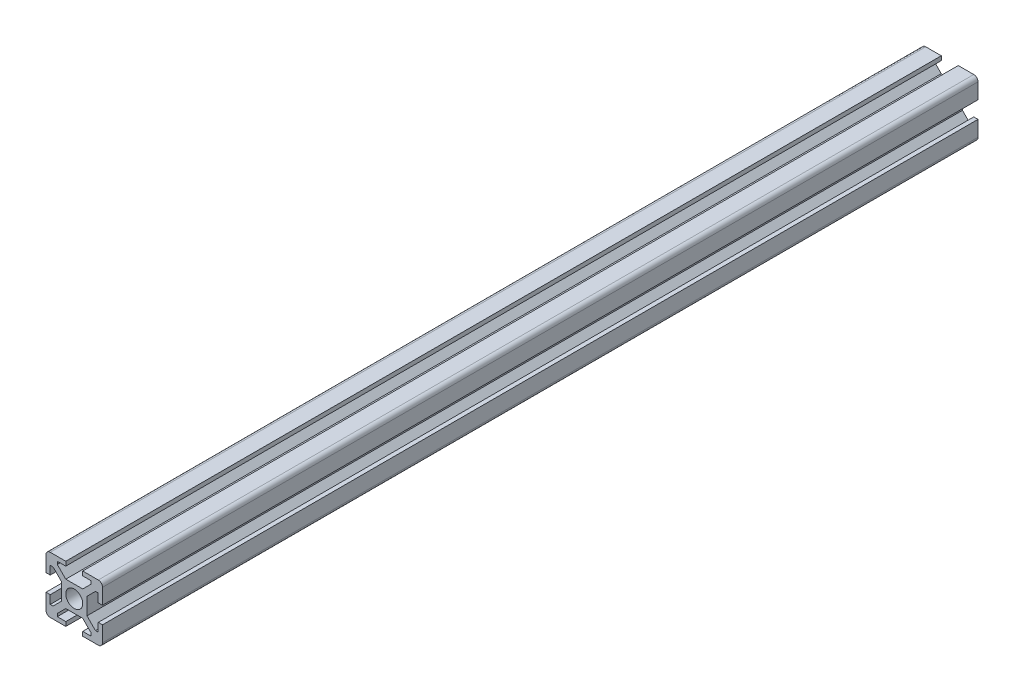
SolidWorks part; units mm, degrees
ref_plane "Plan de face" through (0, 0, 0) normal (0, 0, 1) x (1, 0, 0)
ref_plane "Plan de dessus" through (0, 0, 0) normal (0, 1, 0) x (1, 0, 0)
ref_plane "Plan de droite" through (0, 0, 0) normal (1, 0, 0) x (0, 0, -1)
sketch "Esquisse1" plane through (0, 0, 0) normal (0, 0, 1) x (1, 0, 0)
  line L0 (-10, 10) -> (10, -10) construction
  line L1 (-10, 10) -> (10, 10)
  line L2 (-10, 10) -> (-10, -10)
  line L3 (-10, -10) -> (10, -10)
  line L4 (10, 10) -> (10, -10)
  dimension "D1" = 20
extrude "Extrusion1" add sketch "Esquisse1" along normal mid plane 310
fillet "Congé1" radius 1.5 4 edges at (-10, -10, 0) (10, -10, 0) (-10, 10, 0) (10, 10, 0)
sketch "Esquisse2" plane through (0, 0, -155) normal (0, 0, -1) x (-1, 0, 0)
  line L0 (-10, 3) -> (-10, -3)
  line L1 (-10, -8.5) -> (-10, 8.5) construction
  line L2 (-10, -3) -> (-8.5, -3)
  line L3 (-8.5, -3) -> (-8.5, -6)
  line L4 (-8.5, 6) -> (-7.5, 6)
  line L5 (-4.5, -3) -> (-4.5, 3)
  line L6 (-7.5, 6) -> (-4.5, 3)
  line L7 (-8.5, 6) -> (-8.5, 3)
  line L8 (-8.5, 3) -> (-10, 3)
  line L9 (0, 0) -> (-10, 0) construction
  line L10 (-8.5, -6) -> (-7.5, -6)
  line L11 (-7.5, -6) -> (-4.5, -3)
  point P4 (-10, 0)
  dimension "D1" = 6
  dimension "D2" = 12
  dimension "D3" = 1.5
  dimension "D4" = 5.5
  dimension "D5" = 135
extrude "Enlèv. mat.-Extru.1" cut sketch "Esquisse2" against normal through all
ref_axis "Axe1" through (0, 0, 9.3338) along (0, 0, -1)
pattern_circular "Répétition circulaire1" count 4 over 360 about axis through (0, 0, 9.3338) along (0, 0, -1) of "Enlèv. mat.-Extru.1"
hole_wizard "Trou taraudé M6x1.01" positions "Esquisse4" profile "Esquisse5" tap size "M6x1.0" standard "Ansi Métrique"
sketch "Esquisse4" plane through (0, 0, -155) normal (0, 0, -1) x (-1, 0, 0)
  point P0 (0, 0)
sketch "Esquisse5" plane through (0, 0, -155) normal (1, 0, 0) x (0, 1, 0)
  line L0 (0, 0) -> (0, 31.5022)
  line L1 (0, 31.5022) -> (2.5, 30)
  line L2 (2.5, 30) -> (2.5, 24)
  line L3 (2.5, 24) -> (3, 24)
  line L4 (3, 24) -> (3, 0)
  line L5 (3, 0) -> (0, 0)
  line L10 (0, 31.5022) -> (-2.5, 30) construction
  line L11 (0, -6.35) -> (0, 107.95) construction
  dimension "Diamètre du trou pour taraudage" = 5
  dimension "Profondeur du trou pour taraudage" = 30
  dimension "Diamètre principal du filetage" = 6
  dimension "Profondeur du filetage" = 24
  dimension "Angle de pointe" = 118
mirror "Symétrie1" about plane through (0, 0, 0) normal (0, 0, 1) of "Trou taraudé M6x1.01"
